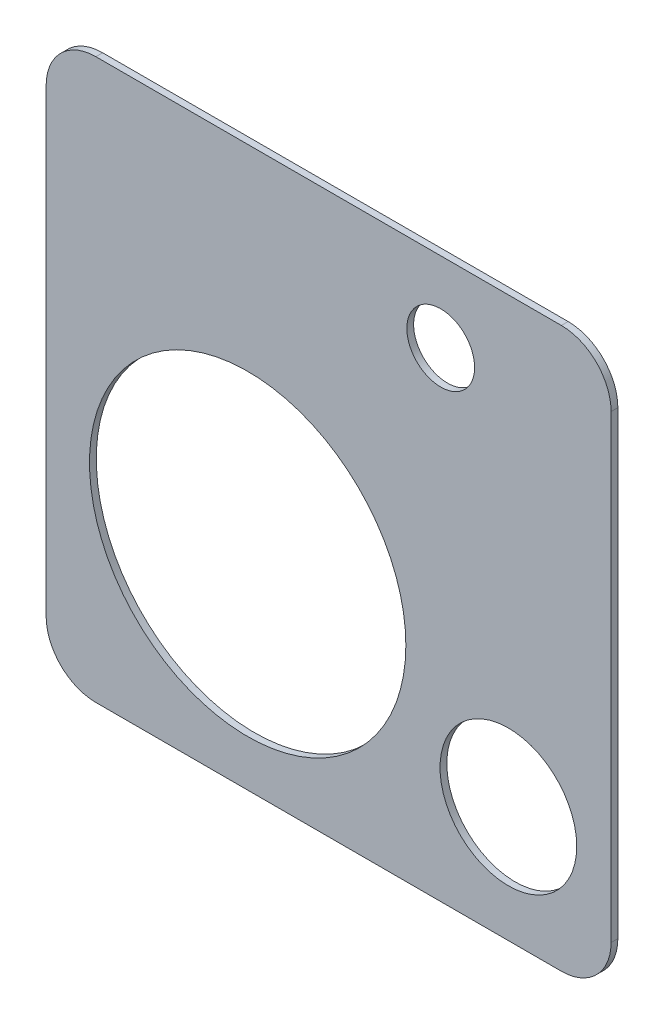
SolidWorks part; units mm, degrees
ref_plane "Front Plane" through (0, 0, 0) normal (0, 0, 1) x (1, 0, 0)
ref_plane "Top Plane" through (0, 0, 0) normal (0, 1, 0) x (1, 0, 0)
ref_plane "Right Plane" through (0, 0, 0) normal (1, 0, 0) x (0, 0, -1)
sketch "Sketch1" plane through (0, 0, 0) normal (0, 0, 1) x (1, 0, 0)
  line L1 (0, 0) -> (500, 0)
  line L2 (0, 0) -> (0, 495)
  line L3 (0, 495) -> (500, 495)
  line L4 (500, 0) -> (500, 495)
  dimension "D1" = 500
  dimension "D2" = 495
extrude "Boss-Extrude1" add sketch "Sketch1" along normal blind 6
fillet "Fillet1" radius 44 4 edges at (0, 0, 3) (500, 0, 3) (0, 495, 3) (500, 495, 3)
sketch "Sketch2" plane through (0, 0, 6) normal (0, 0, 1) x (1, 0, 0)
  circle A0 centre (178.369, 181.0347) radius 156
  dimension "D1" = 312
sketch "Sketch3" plane through (0, 0, 6) normal (0, 0, 1) x (1, 0, 0)
  circle A1 centre (178.369, 181.0347) radius 140
  dimension "D1" = 280
extrude "Cut-Extrude2" cut sketch "Sketch3" against normal through all
sketch "Sketch4" plane through (0, 0, 6) normal (0, 0, 1) x (1, 0, 0)
  circle A0 centre (409.1034, 102.5162) radius 72.5
  point P2 (0, 0)
  point P3 (0, 0)
  point P4 (0, 0)
  dimension "D1" = 145
sketch "Sketch5" plane through (0, 0, 6) normal (0, 0, 1) x (1, 0, 0)
  circle A0 centre (409.1034, 102.5162) radius 60.5
  dimension "D1" = 121
extrude "Cut-Extrude3" cut sketch "Sketch5" against normal through all
sketch "Sketch6" plane through (0, 0, 6) normal (0, 0, 1) x (1, 0, 0)
  line L0 (500, 360) -> (0, 360)
  line L1 (500, 44) -> (500, 451) construction
  line L2 (0, 451) -> (0, 44) construction
  line L3 (44, 0) -> (456, 0) construction
  circle A0 centre (349.2286, 424.3827) radius 50
  circle A1 centre (349.2286, 424.3827) radius 30
  dimension "D1" = 100
  dimension "D3" = 60
  dimension "D2" = 360
extrude "Cut-Extrude5" cut sketch "Sketch6" against normal through all contours A1 region at (349.2286, 424.3827, 6)
